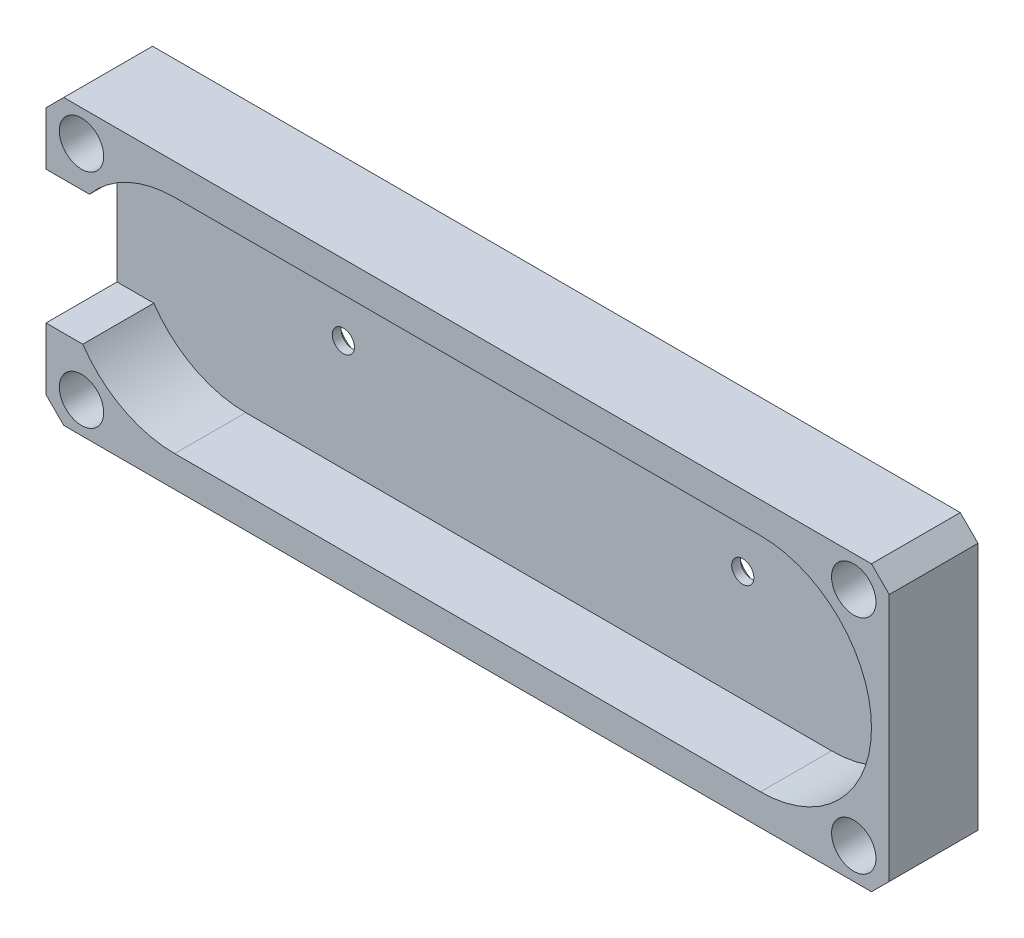
SolidWorks part; units mm, degrees
material "ABS"
ref_plane "前视基准面" through (0, 0, 0) normal (0, 0, 1) x (1, 0, 0)
ref_plane "上视基准面" through (0, 0, 0) normal (0, 1, 0) x (1, 0, 0)
ref_plane "右视基准面" through (0, 0, 0) normal (1, 0, 0) x (0, 0, -1)
other "Configuration Table"
sketch "草图1" plane through (0, 0, 0) normal (0, 0, 1) x (1, 0, 0)
  line L0 (-158.5309, -7.0864) -> (-223.5309, -7.0864) construction
  line L1 (-144.0309, 8.9136) -> (-239.0309, 8.9136)
  line L2 (-144.0309, 8.9136) -> (-144.0309, -23.0864)
  line L3 (-144.0309, -23.0864) -> (-239.0309, -23.0864)
  line L4 (-239.0309, 8.9136) -> (-239.0309, -23.0864)
  line L5 (-144.0309, 8.9136) -> (-239.0309, -23.0864) construction
  line L6 (-144.0309, -23.0864) -> (-239.0309, 8.9136) construction
  line L7 (-158.5309, -19.5864) -> (-223.5309, -19.5864) construction
  line L8 (-158.5309, 5.4136) -> (-223.5309, 5.4136) construction
  line L9 (-191.5309, 8.9136) -> (-191.5309, -23.0864) construction
  arc A0 (-158.5309, -19.5864) -> (-158.5309, 5.4136) centre (-158.5309, -7.0864) ccw construction
  arc A1 (-223.5309, 5.4136) -> (-223.5309, -19.5864) centre (-223.5309, -7.0864) ccw construction
  circle A2 centre (-168.5309, -7.0864) radius 1.25
  circle A3 centre (-213.5309, -7.0864) radius 1.25
  circle A4 centre (-147.7809, -19.3364) radius 1.25 construction
  circle A5 centre (-235.2809, 5.1636) radius 1.25 construction
  circle A6 centre (-235.2809, 5.1636) radius 2.8 construction
  point P4 (-191.5309, -7.0864)
  point P7 (-191.0309, -7.0864)
  point P18 (-191.5309, -7.0864)
  point P20 (-158.5309, -5.3999)
  point P25 (-144.0309, -7.0864)
  dimension "D1" = 90
  dimension "D5" = 45
  dimension "D6" = 2.5
  dimension "D8" = 2.5
  dimension "D9" = 2.5
  dimension "D11" = 2.5
  dimension "D12" = 2.5
  dimension "D13" = 5.6
  dimension "D15" = 22.5
  dimension "D2" = 25
  dimension "D3" = 95
  dimension "D4" = 32
  dimension "D10" = 2.5
  dimension "D14" = 2
  dimension "D16" = 10
extrude "凸台-拉伸1" add sketch "草图1" along normal blind 2
chamfer "倒角1" distance 2 angle 45 4 edges at (-144.0309, -23.0864, 1) (-144.0309, 8.9136, 1) (-239.0309, -23.0864, 1) (-239.0309, 8.9136, 1)
sketch "草图3" plane through (0, 0, 2) normal (0, 0, 1) x (1, 0, 0)
  line L4 (-144.0309, -21.0864) -> (-144.0309, 6.9136)
  line L5 (-146.0309, 8.9136) -> (-237.0309, 8.9136)
  line L6 (-239.0309, 6.9136) -> (-239.0309, -21.0864)
  line L7 (-237.0309, -23.0864) -> (-146.0309, -23.0864)
  line L8 (-144.0309, -21.0864) -> (-144.0309, 6.9136)
  line L9 (-146.0309, 8.9136) -> (-237.0309, 8.9136)
  line L10 (-239.0309, 6.9136) -> (-239.0309, -21.0864)
  line L11 (-237.0309, -23.0864) -> (-146.0309, -23.0864)
  line L12 (-146.8594, 6.9136) -> (-236.2025, 6.9136)
  line L13 (-236.2025, 6.9136) -> (-237.0309, 6.0852)
  line L14 (-237.0309, 6.0852) -> (-237.0309, -20.2579)
  line L15 (-237.0309, -20.2579) -> (-236.2025, -21.0864)
  line L16 (-236.2025, -21.0864) -> (-146.8594, -21.0864)
  line L17 (-146.8594, -21.0864) -> (-146.0309, -20.2579)
  line L18 (-146.0309, -20.2579) -> (-146.0309, 6.0852)
  line L19 (-146.0309, 6.0852) -> (-146.8594, 6.9136)
  line L20 (-146.0309, -23.0864) -> (-144.0309, -21.0864)
  line L21 (-146.0309, -23.0864) -> (-144.0309, -21.0864)
  line L22 (-144.0309, 6.9136) -> (-146.0309, 8.9136)
  line L23 (-144.0309, 6.9136) -> (-146.0309, 8.9136)
  line L24 (-237.0309, 8.9136) -> (-239.0309, 6.9136)
  line L25 (-237.0309, 8.9136) -> (-239.0309, 6.9136)
  line L26 (-239.0309, -21.0864) -> (-237.0309, -23.0864)
  line L27 (-239.0309, -21.0864) -> (-237.0309, -23.0864)
  dimension "D1" = 0
  dimension "D2" = 2
extrude "凸台-拉伸2" add sketch "草图3" along normal blind 8
sketch "草图4" plane through (0, 0, 2) normal (0, 0, 1) x (1, 0, 0)
  line L0 (-236.2025, -21.0864) -> (-146.8594, -21.0864) construction
  line L1 (-146.8594, -21.0864) -> (-146.0309, -20.2579) construction
  line L4 (-146.0309, -20.2579) -> (-146.0309, 6.0852) construction
  line L5 (-146.8594, 6.9136) -> (-236.2025, 6.9136) construction
  line L6 (-236.2025, 6.9136) -> (-237.0309, 6.0852) construction
  line L7 (-237.0309, 6.0852) -> (-237.0309, -20.2579) construction
  line L8 (-151.0309, -21.0864) -> (-146.8594, -21.0864)
  line L9 (-146.8594, -21.0864) -> (-146.0309, -20.2579)
  line L10 (-146.0309, -20.2579) -> (-146.0309, -16.0864)
  line L11 (-232.0309, 6.9136) -> (-236.2025, 6.9136)
  line L12 (-236.2025, 6.9136) -> (-237.0309, 6.0852)
  line L13 (-237.0309, 6.0852) -> (-237.0309, 1.9136)
  line L14 (-232.0309, 4.4136) -> (-232.0309, 6.9136)
  line L15 (-234.5309, 1.9136) -> (-237.0309, 1.9136)
  line L16 (-148.5309, -16.0864) -> (-146.0309, -16.0864)
  line L17 (-151.0309, -18.5864) -> (-151.0309, -21.0864)
  arc A0 (-234.5309, 1.9136) -> (-232.0309, 4.4136) centre (-234.5309, 4.4136) ccw
  circle A1 centre (-148.5309, -18.5864) radius 1.25
  circle A2 centre (-234.5309, 4.4136) radius 1.25
  arc A3 (-148.5309, -16.0864) -> (-151.0309, -18.5864) centre (-148.5309, -18.5864) ccw
  dimension "D3" = 5
  dimension "D4" = 2.5
  dimension "D5" = 2.5
  dimension "D6" = 5
extrude "凸台-拉伸3" [suppressed] add sketch "草图4" along normal blind 13
sketch "草图5" plane through (-239.0309, 0, 0) normal (-1, 0, 0) x (0, 0, 1)
  line L0 (10, 6.9136) -> (10, -21.0864) construction
  line L1 (10, 0.9136) -> (2, 0.9136)
  line L2 (10, 0.9136) -> (10, -14.0864)
  line L3 (10, -14.0864) -> (2, -14.0864)
  line L4 (2, 0.9136) -> (2, -14.0864)
  line L5 (10, 0.9136) -> (2, -14.0864) construction
  line L6 (10, -14.0864) -> (2, 0.9136) construction
  line L7 (0, 8.9136) -> (10, 8.9136) construction
  line L8 (19.8161, -6.5864) -> (0, -6.5864) construction
  line L9 (0, 6.9136) -> (0, -21.0864) construction
  point P4 (6, -6.5864)
  line M10 (10, -21.0864) -> (10, 6.9136)
  dimension "D1" = 15
  dimension "D2" = 8
  dimension "D4" = 15.5
extrude "切除-拉伸1" cut sketch "草图5" against normal blind 3.5 contours L1 L4 L3 M10 region at (-239.0309, -6.5864, 6)
sketch "草图6" [suppressed] plane through (0, 0, 2) normal (0, 0, 1) x (1, 0, 0)
  line L0 (-146.0309, -16.0864) -> (-146.0309, 6.0852) construction
  line L1 (-146.8594, 6.9136) -> (-232.0309, 6.9136) construction
  line L2 (-236.2025, -21.0864) -> (-151.0309, -21.0864) construction
  line L3 (-146.1442, 4.4136) -> (-147.5876, 6.9136) construction
  line L4 (-147.5876, 6.9136) -> (-150.4743, 6.9136) construction
  line L5 (-150.4743, 6.9136) -> (-151.9177, 4.4136) construction
  line L6 (-151.9177, 4.4136) -> (-150.4743, 1.9136) construction
  line L7 (-150.4743, 1.9136) -> (-147.5876, 1.9136) construction
  line L8 (-147.5876, 1.9136) -> (-146.1442, 4.4136) construction
  line L9 (-237.0309, -14.0864) -> (-237.0309, -20.2579) construction
  circle A0 centre (-149.0309, 4.4136) radius 1.25
  circle A1 centre (-234.0309, -18.5864) radius 1.25
  circle A3 centre (-149.0309, 4.4136) radius 2.5 construction
  circle A4 centre (-234.5309, 4.4136) radius 1.25
  circle A5 centre (-148.5309, -18.5864) radius 1.25
  circle A8 centre (-234.5309, 4.4136) radius 1.25 construction
  circle A9 centre (-148.5309, -18.5864) radius 1.25 construction
  dimension "D1" = 2.5
  dimension "D2" = 3
  dimension "D5" = 2.5
  dimension "D6" = 3
  dimension "D3" = 2.5
  dimension "D4" = 5
extrude "切除-拉伸2" [suppressed] cut sketch "草图6" against normal blind 10 contours A5 | A0 | A4 | A1
sketch "草图7" plane through (0, 0, 0) normal (0, 0, -1) x (-1, 0, 0)
  circle A0 centre (168.5309, -7.0864) radius 2.5
  circle A1 centre (213.5309, -7.0864) radius 2.5
  dimension "D1" = 5
extrude "切除-拉伸3" cut sketch "草图7" against normal blind 1
sketch "草图8" [suppressed] plane through (0, 0, 15) normal (0, 0, 1) x (1, 0, 0)
  line L0 (-213.5309, -5.5864) -> (-223.5309, -5.5864) construction
  line L5 (-232.0309, 4.4136) -> (-232.0309, 6.9136)
  line L6 (-232.0309, 6.9136) -> (-236.2025, 6.9136)
  line L7 (-236.2025, 6.9136) -> (-237.0309, 6.0852)
  line L8 (-237.0309, 6.0852) -> (-237.0309, 1.9136)
  line L9 (-237.0309, 1.9136) -> (-234.5309, 1.9136)
  arc A0 (-232.0367, 4.2449) -> (-234.1259, 1.9467) centre (-223.5309, -5.5864) ccw
  arc A2 (-234.5309, 1.9136) -> (-232.0309, 4.4136) centre (-234.5309, 4.4136) ccw
  arc A3 (-234.1259, 1.9467) -> (-232.0367, 4.2449) centre (-234.5309, 4.4136) ccw
  arc M8 (-234.5309, 1.9136) -> (-232.0309, 4.4136) centre (-234.5309, 4.4136) ccw
  dimension "D2" = 13
  dimension "D3" = 10
  dimension "D1" = 0
extrude "切除-拉伸4" [suppressed] cut sketch "草图8" against normal blind 6 contours A0 M8
sketch "草图9" plane through (0, 0, 2) normal (0, 0, 1) x (1, 0, 0)
  line L0 (-213.5309, -7.0864) -> (-168.5309, -7.0864) construction
  line L1 (-224.5309, -7.0864) -> (-158.5309, -7.0864) construction
  line L2 (-224.5309, 5.4136) -> (-158.5309, 5.4136)
  line L3 (-224.5309, -19.5864) -> (-158.5309, -19.5864)
  line L4 (-191.5309, -7.0864) -> (-191.5309, 8.9136) construction
  line L5 (-146.0309, 8.9136) -> (-237.0309, 8.9136) construction
  line L6 (-237.0309, 0.9136) -> (-234.1356, 0.9136)
  line L7 (-237.0309, -14.0864) -> (-234.8871, -14.0864)
  line L18 (-237.0309, 6.0852) -> (-237.0309, 0.9136)
  line L19 (-237.0309, 0.9136) -> (-239.0309, 0.9136)
  line L20 (-239.0309, 0.9136) -> (-239.0309, -14.0864)
  line L21 (-239.0309, -14.0864) -> (-237.0309, -14.0864)
  line L22 (-237.0309, -14.0864) -> (-237.0309, -20.2579)
  line L23 (-237.0309, -20.2579) -> (-236.2025, -21.0864)
  line L24 (-236.2025, -21.0864) -> (-146.8594, -21.0864)
  line L25 (-146.8594, -21.0864) -> (-146.0309, -20.2579)
  line L26 (-146.0309, -20.2579) -> (-146.0309, 6.0852)
  line L27 (-146.0309, 6.0852) -> (-146.8594, 6.9136)
  line L28 (-146.8594, 6.9136) -> (-236.2025, 6.9136)
  line L29 (-236.2025, 6.9136) -> (-237.0309, 6.0852)
  line L30 (-237.0309, 6.0852) -> (-237.0309, 0.9136)
  line L31 (-237.0309, 0.9136) -> (-239.0309, 0.9136) construction
  line L32 (-239.0309, 0.9136) -> (-239.0309, -14.0864) construction
  line L33 (-239.0309, -14.0864) -> (-237.0309, -14.0864) construction
  line L34 (-237.0309, -14.0864) -> (-237.0309, -20.2579)
  line L35 (-237.0309, -20.2579) -> (-236.2025, -21.0864)
  line L36 (-236.2025, -21.0864) -> (-146.8594, -21.0864)
  line L37 (-146.8594, -21.0864) -> (-146.0309, -20.2579)
  line L38 (-146.0309, -20.2579) -> (-146.0309, 6.0852)
  line L39 (-146.0309, 6.0852) -> (-146.8594, 6.9136)
  line L40 (-146.8594, 6.9136) -> (-236.2025, 6.9136)
  line L41 (-236.2025, 6.9136) -> (-237.0309, 6.0852)
  arc A0 (-224.5309, 5.4136) -> (-224.5309, -19.5864) centre (-224.5309, -7.0864) ccw
  arc A1 (-158.5309, -19.5864) -> (-158.5309, 5.4136) centre (-158.5309, -7.0864) ccw
  circle A3 centre (-213.5309, -7.0864) radius 1.25 construction
  circle A4 centre (-168.5309, -7.0864) radius 1.25 construction
  point P4 (-191.5309, -7.0864)
  line M24 (-237.0309, 6.0852) -> (-237.0309, 0.9136)
  line M28 (-237.0309, -14.0864) -> (-237.0309, -20.2579)
  line M29 (-237.0309, -20.2579) -> (-236.2025, -21.0864)
  line M30 (-236.2025, -21.0864) -> (-146.8594, -21.0864)
  line M31 (-146.8594, -21.0864) -> (-146.0309, -20.2579)
  line M32 (-146.0309, -20.2579) -> (-146.0309, 6.0852)
  line M33 (-146.0309, 6.0852) -> (-146.8594, 6.9136)
  line M34 (-146.8594, 6.9136) -> (-236.2025, 6.9136)
  line M35 (-236.2025, 6.9136) -> (-237.0309, 6.0852)
  dimension "D2" = 91
  dimension "D1" = 25
  dimension "D3" = 0
extrude "凸台-拉伸4" add sketch "草图9" along normal up to surface (8 mm away) contours A1 L3 A0 L7 L6 L2 M28 M29 M30 M31 M32 M33 M34 M35 M24 | A1 L3 A0 L7 M28 M29 M30 M31 M32 region at (-230.2249, 5.0666, 2) region at (-146.9517, -13.6722, 2) up to face at (-200.8309, -6.9864, 10)
sketch "草图10" plane through (0, 0, 10) normal (0, 0, 1) x (1, 0, 0)
  line L0 (-237.0309, -23.0864) -> (-146.0309, -23.0864) construction
  line L1 (-144.0309, -21.0864) -> (-144.0309, 6.9136) construction
  line L2 (-191.5309, -23.0864) -> (-191.5309, 8.9136) construction
  line L3 (-146.0309, 8.9136) -> (-237.0309, 8.9136) construction
  circle A0 centre (-148.0309, -19.5864) radius 2.5
  circle A1 centre (-235.0309, -19.5864) radius 2.5
  circle A2 centre (-148.0309, 5.4136) radius 2.5
  circle A3 centre (-235.0309, 5.4136) radius 2.5
  dimension "D1" = 5
  dimension "D2" = 3.5
  dimension "D3" = 4
  dimension "D4" = 5
  dimension "D5" = 3.5
  dimension "D6" = 4
extrude "切除-拉伸5" cut sketch "草图10" against normal through all
